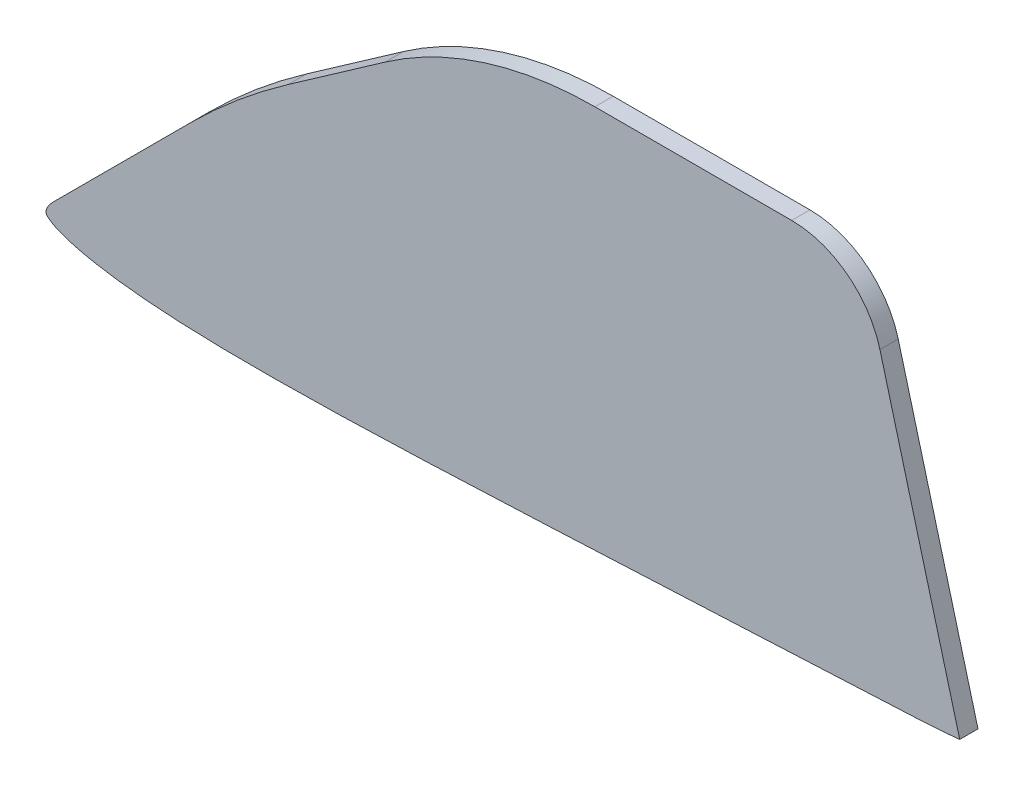
SolidWorks part; units mm, degrees
material "Polyurethane Foam Flexible"
ref_plane "Front Plane" through (0, 0, 0) normal (0, 0, 1) x (1, 0, 0)
ref_plane "Top Plane" through (0, 0, 0) normal (0, 1, 0) x (1, 0, 0)
ref_plane "Right Plane" through (0, 0, 0) normal (1, 0, 0) x (0, 0, -1)
curve "Curve1"
  spline degree 3 poles (319.3399, -0.0631, 0) (320.1749, 0.0121, 0) (319.2775, -0.0304, 0) (318.5408, -0.0213, 0) (316.7306, 0.0124, 0) (314.5198, 0.1434, 0) (311.6513, 0.3645, 0) (308.3098, 0.7064, 0) (304.5223, 1.1688, 0) (300.3775, 1.7342, 0) (295.943, 2.3803, 0) (291.2893, 3.0786, 0) (286.4795, 3.7953, 0) (281.5654, 4.4835, 0) (276.5911, 5.1112, 0) (271.5953, 5.6552, 0) (266.6171, 6.1013, 0) (261.6991, 6.4472, 0) (256.8868, 6.6894, 0) (252.2271, 6.822, 0) (247.7645, 6.8415, 0) (243.539, 6.7385, 0) (239.586, 6.5122, 0) (235.9364, 6.165, 0) (232.6179, 5.7039, 0) (229.6553, 5.1389, 0) (227.0686, 4.4832, 0) (224.8731, 3.7453, 0) (223.0782, 2.9469, 0) (221.6854, 2.1189, 0) (220.7273, 1.3252, 0) (220.2338, 0.7064, 0) (220.0616, 0.3184, 0) (220.0116, 0.1395, 0) (219.9959, -0.0029, 0) (220.0081, -0.1155, 0) (220.062, -0.2184, 0) (220.1603, -0.338, 0) (220.3145, -0.4779, 0) (220.4826, -0.5989, 0) (220.9421, -0.8937, 0) (221.8924, -1.2976, 0) (223.5205, -1.784, 0) (225.624, -2.2279, 0) (228.1771, -2.6133, 0) (231.1641, -2.9192, 0) (234.5635, -3.137, 0) (238.352, -3.2671, 0) (242.4996, -3.312, 0) (246.9689, -3.2849, 0) (251.716, -3.1932, 0) (256.6914, -3.0476, 0) (261.8415, -2.8575, 0) (267.1088, -2.6383, 0) (272.4315, -2.3988, 0) (277.7457, -2.1515, 0) (282.9865, -1.902, 0) (288.0894, -1.6584, 0) (292.9917, -1.4233, 0) (297.6334, -1.202, 0) (301.9578, -0.9952, 0) (305.9103, -0.8085, 0) (309.4451, -0.64, 0) (312.5051, -0.4927, 0) (315.0892, -0.3596, 0) (317.0641, -0.2502, 0) (318.6672, -0.1355, 0) (319.3399, -0.0631, 0) (320.1749, 0.0121, 0) (319.2775, -0.0304, 0) knots -0.013413 -0.006112 -0.001576 0 0.001644 0.006617 0.014862 0.026171 0.040322 0.057038 0.075955 0.096697 0.118903 0.142213 0.166278 0.190806 0.215581 0.240407 0.265107 0.28948 0.3133 0.336346 0.3584 0.379278 0.398833 0.416933 0.433472 0.448354 0.461506 0.472899 0.482558 0.490505 0.496775 0.500889 0.502032 0.503032 0.503621 0.504144 0.50468 0.505311 0.506426 0.507746 0.50837 0.514497 0.522892 0.533497 0.546244 0.561059 0.577879 0.596602 0.617103 0.639204 0.662686 0.687305 0.712801 0.738887 0.765254 0.791583 0.817549 0.842832 0.867121 0.890118 0.911544 0.931132 0.948636 0.963834 0.976537 0.986587 0.993888 0.998424 1 1.001644 1.006617 1.014862 periodic
sketch "Sketch1" plane through (0, 0, 0) normal (0, 0, 1) x (1, 0, 0)
  line L0 (320, 0) -> (320, 24.575) construction
  line L1 (220.7656, 1.3114) -> (240.7656, 21.3114)
  line L2 (240.7656, 21.3114) -> (267.4557, 40)
  line L3 (309.282, 40) -> (320, 0)
  line L4 (220.7656, 1.3114) -> (220.7656, 28.3519) construction
  line L5 (267.4557, 40) -> (309.282, 40)
  spline S0 degree 3 poles (319.3399, -0.0631) (320.1749, 0.0121) (319.2775, -0.0304) (318.5408, -0.0213) (316.7306, 0.0124) (314.5198, 0.1434) (311.6513, 0.3645) (308.3098, 0.7064) (304.5223, 1.1688) (300.3775, 1.7342) (295.943, 2.3803) (291.2893, 3.0786) (286.4795, 3.7953) (281.5654, 4.4835) (276.5911, 5.1112) (271.5953, 5.6552) (266.6171, 6.1013) (261.6991, 6.4472) (256.8868, 6.6894) (252.2271, 6.822) (247.7645, 6.8415) (243.539, 6.7385) (239.586, 6.5122) (235.9364, 6.165) (232.6179, 5.7039) (229.6553, 5.1389) (227.0686, 4.4832) (224.8731, 3.7453) (223.0782, 2.9469) (221.6854, 2.1189) (220.7273, 1.3252) (220.2338, 0.7064) (220.0616, 0.3184) (220.0116, 0.1395) (219.9959, -0.0029) (220.0081, -0.1155) (220.062, -0.2184) (220.1603, -0.338) (220.3145, -0.4779) (220.4826, -0.5989) (220.9421, -0.8937) (221.8924, -1.2976) (223.5205, -1.784) (225.624, -2.2279) (228.1771, -2.6133) (231.1641, -2.9192) (234.5635, -3.137) (238.352, -3.2671) (242.4996, -3.312) (246.9689, -3.2849) (251.716, -3.1932) (256.6914, -3.0476) (261.8415, -2.8575) (267.1088, -2.6383) (272.4315, -2.3988) (277.7457, -2.1515) (282.9865, -1.902) (288.0894, -1.6584) (292.9917, -1.4233) (297.6334, -1.202) (301.9578, -0.9952) (305.9103, -0.8085) (309.4451, -0.64) (312.5051, -0.4927) (315.0892, -0.3596) (317.0641, -0.2502) (318.6672, -0.1355) (319.3399, -0.0631) (320.1749, 0.0121) (319.2775, -0.0304) knots -0.013413 -0.006112 -0.001576 0 0.001644 0.006617 0.014862 0.026171 0.040322 0.057038 0.075955 0.096697 0.118903 0.142213 0.166278 0.190806 0.215581 0.240407 0.265107 0.28948 0.3133 0.336346 0.3584 0.379278 0.398833 0.416933 0.433472 0.448354 0.461506 0.472899 0.482558 0.490505 0.496775 0.500889 0.502032 0.503032 0.503621 0.504144 0.50468 0.505311 0.506426 0.507746 0.50837 0.514497 0.522892 0.533497 0.546244 0.561059 0.577879 0.596602 0.617103 0.639204 0.662686 0.687305 0.712801 0.738887 0.765254 0.791583 0.817549 0.842832 0.867121 0.890118 0.911544 0.931132 0.948636 0.963834 0.976537 0.986587 0.993888 0.998424 1 1.001644 1.006617 1.014862 only from (320, 0) to (320, 0) construction
  spline S1 degree 3 poles (319.3399, -0.0631) (320.1749, 0.0121) (319.2775, -0.0304) (318.5408, -0.0213) (316.7306, 0.0124) (314.5198, 0.1434) (311.6513, 0.3645) (308.3098, 0.7064) (304.5223, 1.1688) (300.3775, 1.7342) (295.943, 2.3803) (291.2893, 3.0786) (286.4795, 3.7953) (281.5654, 4.4835) (276.5911, 5.1112) (271.5953, 5.6552) (266.6171, 6.1013) (261.6991, 6.4472) (256.8868, 6.6894) (252.2271, 6.822) (247.7645, 6.8415) (243.539, 6.7385) (239.586, 6.5122) (235.9364, 6.165) (232.6179, 5.7039) (229.6553, 5.1389) (227.0686, 4.4832) (224.8731, 3.7453) (223.0782, 2.9469) (221.6854, 2.1189) (220.7273, 1.3252) (220.2338, 0.7064) (220.0616, 0.3184) (220.0116, 0.1395) (219.9959, -0.0029) (220.0081, -0.1155) (220.062, -0.2184) (220.1603, -0.338) (220.3145, -0.4779) (220.4826, -0.5989) (220.9421, -0.8937) (221.8924, -1.2976) (223.5205, -1.784) (225.624, -2.2279) (228.1771, -2.6133) (231.1641, -2.9192) (234.5635, -3.137) (238.352, -3.2671) (242.4996, -3.312) (246.9689, -3.2849) (251.716, -3.1932) (256.6914, -3.0476) (261.8415, -2.8575) (267.1088, -2.6383) (272.4315, -2.3988) (277.7457, -2.1515) (282.9865, -1.902) (288.0894, -1.6584) (292.9917, -1.4233) (297.6334, -1.202) (301.9578, -0.9952) (305.9103, -0.8085) (309.4451, -0.64) (312.5051, -0.4927) (315.0892, -0.3596) (317.0641, -0.2502) (318.6672, -0.1355) (319.3399, -0.0631) (320.1749, 0.0121) (319.2775, -0.0304) knots -0.013413 -0.006112 -0.001576 0 0.001644 0.006617 0.014862 0.026171 0.040322 0.057038 0.075955 0.096697 0.118903 0.142213 0.166278 0.190806 0.215581 0.240407 0.265107 0.28948 0.3133 0.336346 0.3584 0.379278 0.398833 0.416933 0.433472 0.448354 0.461506 0.472899 0.482558 0.490505 0.496775 0.500889 0.502032 0.503032 0.503621 0.504144 0.50468 0.505311 0.506426 0.507746 0.50837 0.514497 0.522892 0.533497 0.546244 0.561059 0.577879 0.596602 0.617103 0.639204 0.662686 0.687305 0.712801 0.738887 0.765254 0.791583 0.817549 0.842832 0.867121 0.890118 0.911544 0.931132 0.948636 0.963834 0.976537 0.986587 0.993888 0.998424 1 1.001644 1.006617 1.014862 only from (320, 0) to (320, 0)
  dimension "D1" = 45
  dimension "D2" = 20
  dimension "D3" = 55
  dimension "D4" = 15
  dimension "D5" = 40
extrude "Boss-Extrude1" add sketch "Sketch1" along normal blind 2 contours S1 | S1 region at (279.7537, 19.7994, 0) region at (259.0166, 1.412, 0)
fillet "Fillet2" radius 10 1 edges at (309.282, 40, 1)
fillet "Fillet3" radius 40 1 edges at (267.4557, 40, 1)
fillet "Fillet4" radius 80 1 edges at (240.7656, 21.3114, 1)
